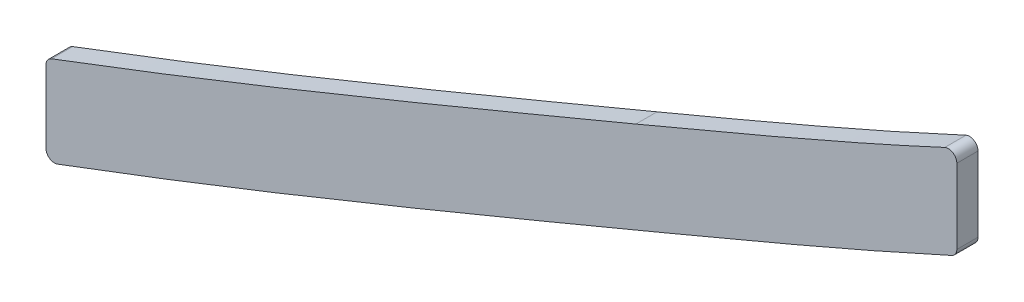
SolidWorks part; units mm, degrees
material "Balsa"
ref_plane "Front Plane" through (0, 0, 0) normal (0, 0, 1) x (1, 0, 0)
ref_plane "Top Plane" through (0, 0, 0) normal (0, 1, 0) x (1, 0, 0)
ref_plane "Right Plane" through (0, 0, 0) normal (1, 0, 0) x (0, 0, -1)
sketch "Sketch1" plane through (0, 0, 0) normal (0, 0, 1) x (1, 0, 0)
  line L0 (129.1265, 126.0779) -> (45.2335, 95.7177) construction
  line L1 (0, 0) -> (0, 656.1291) construction
  line L2 (1046.2855, -53.4707) -> (499.61, -53.4707)
  line L3 (210.5585, 160.3278) -> (162.5016, 140.2562) construction
  line L4 (103.1875, 116.7756) -> (103.1875, 13.8211)
  line L5 (239.7125, 173.3723) -> (239.7125, 18.8603)
  line L6 (239.2308, 173.1465) -> (239.7125, 173.3723)
  line L8 (244.6214, 161.6473) -> (245.1031, 161.8731) construction
  arc A3 (36.5452, 91.5722) -> (50.6762, 98.5918) centre (72.503, 36.9197) cw
  arc A4 (33.5941, 89.512) -> (36.5452, 91.5722) centre (72.5029, 36.9192) cw
  arc A5 (26.5879, 83.5209) -> (26.7433, 83.6735) centre (72.5028, 36.9189) cw
  spline S0 degree 3 poles (90.5238, 112.1079) (125.4792, 124.758) (161.5722, 139.868) (191.6078, 152.4128) knots 0 0 0 0 1 1 1 1
  spline S1 degree 1 poles (94.8455, 100.1658) (196.5024, 140.6938) knots 0 0 1 1 construction
  spline S2 degree 1 poles (196.5024, 140.6938) (244.6214, 161.6473) knots 0 0 1 1 construction
  spline S3 degree 3 poles (94.8455, 100.1658) (99.2852, 101.7725) (108.1262, 105.0368) (121.4387, 110.1165) (134.6545, 115.2971) (147.7092, 120.5264) (160.5147, 125.7437) (170.9096, 130.0328) (179.0169, 133.3991) (184.9834, 135.8842) (189.8481, 137.9146) (193.6777, 139.514) (195.5579, 140.2994) (196.5024, 140.6938) knots 0 0 0 0 0.125 0.25 0.375 0.5 0.625 0.75 0.8125 0.875 0.9375 0.96875 1 1 1 1
  spline S4 degree 3 poles (196.5024, 140.6938) (200.4723, 142.3519) (208.3835, 145.6702) (220.3642, 150.772) (230.4226, 155.1671) (238.5139, 158.8124) (242.5935, 160.6966) (244.6214, 161.6473) knots 14.81781 14.81781 14.81781 14.81781 16.034279 17.250748 18.467217 19.075451 19.683685 19.683685 19.683685 19.683685
  spline S8 degree 5 poles (191.6078, 152.4128) (201.0734, 156.3662) (210.5667, 160.3662) (220.0964, 164.4424) (229.6613, 168.6605) (239.2308, 173.1465) knots 14.81781 14.81781 14.81781 14.81781 14.81781 14.81781 19.683685 19.683685 19.683685 19.683685 19.683685 19.683685 weights 1 1 1 1 1 1
  spline S9 degree 5 poles (50.6762, 98.5918) (58.5981, 101.1149) (66.52, 103.702) (74.4715, 106.3907) (82.4705, 109.1935) (90.5238, 112.1079) knots 0 0 0 0 0 0 4.296847 4.296847 4.296847 4.296847 4.296847 4.296847 weights 1 1 1 1 1 1
  spline S10 degree 5 poles (26.7433, 83.6735) (28.0126, 84.9158) (29.3241, 86.115) (30.6979, 87.2902) (32.127, 88.4267) (33.5941, 89.512) knots 0 0 0 0 0 0 0.963167 0.963167 0.963167 0.963167 0.963167 0.963167 weights 1 1 1 1 1 1
  spline S11 degree 5 poles (18.4363, 73.7529) (19.8463, 75.8225) (21.3553, 77.8246) (22.9948, 79.8016) (24.7465, 81.7067) (26.5879, 83.5209) knots 0 0 0 0 0 0 1.402615 1.402615 1.402615 1.402615 1.402615 1.402615 weights 1 1 1 1 1 1
  spline S12 degree 5 poles (818.067, 264.7065) (827.0431, 263.4992) (836.0291, 262.3734) (845.0868, 261.3058) (891.3865, 256.087) (937.6862, 251.7792) (973.4521, 248.2277) (1071.9467, 239.0511) (1170.4413, 229.7315) (1231.7919, 224.5039) (1324.8993, 216.7906) (1418.0067, 209.0401) (1449.7429, 206.3618) (1636.9286, 190.5211) (1824.1143, 175.4092) (1979.9669, 164.2997) (2156.2686, 150.4144) (2332.5703, 133.8572) (2354.213, 131.7851) (2436.3555, 123.724) (2518.4981, 114.8591) (2579.4813, 107.7425) (2639.6368, 100.3834) (2699.7923, 92.6045) knots 77.930822 77.930822 77.930822 77.930822 77.930822 77.930822 82.465793 82.465793 82.465793 100.79329 100.79329 100.79329 131.098954 131.098954 131.098954 146.769198 146.769198 146.769198 223.533959 223.533959 223.533959 233.943117 233.943117 233.943117 264.216209 264.216209 264.216209 264.216209 264.216209 264.216209 weights 1 1 1 1 1 1 1 1 1 1 1 1 1 1 1 1 1 1 1 1 1 1 1 1
  spline S13 degree 5 poles (241.4251, -53.4707) (224.2869, -53.4707) (207.1495, -53.4673) (190.2039, -52.6866) (151.6561, -49.0319) (113.1083, -41.5037) (91.9499, -36.3426) (71.313, -30.9696) (50.6762, -24.7565) knots 0 0 0 0 0 0 8.713816 8.713816 8.713816 19.90683 19.90683 19.90683 19.90683 19.90683 19.90683 weights 1 1 1 1 1 1 1 1 1
  spline S14 degree 5 poles (499.61, -53.4707) (492.1368, -53.4707) (484.7543, -53.4707) (477.443, -53.4707) (448.5166, -53.4707) (419.5901, -53.4707) (398.3681, -53.4707) (355.6475, -53.4707) (312.927, -53.4707) (289.2351, -53.4703) (265.365, -53.4707) (241.4948, -53.4707) (241.4716, -53.4707) (241.4484, -53.4707) (241.4251, -53.4707) knots 19.90683 19.90683 19.90683 19.90683 19.90683 19.90683 23.637897 23.637897 23.637897 34.276546 34.276546 34.276546 46.401341 46.401341 46.401341 46.413154 46.413154 46.413154 46.413154 46.413154 46.413154 weights 1 1 1 1 1 1 1 1 1 1 1 1 1 1 1
  spline S15 degree 5 poles (2699.7923, -7.5245) (2639.6368, -11.6572) (2579.4813, -15.4358) (2518.4981, -19.1485) (2436.3555, -23.2524) (2354.213, -26.6315) (2332.5703, -27.481) (2156.2686, -34.3778) (1979.9669, -41.6286) (1824.1143, -52.7713) (1636.9286, -53.5796) (1449.7429, -53.454) (1418.0067, -53.4707) (1324.8993, -53.4707) (1231.7919, -53.4707) (1170.4413, -53.4707) (1108.7841, -53.4707) (1047.1269, -53.4707) (1046.8464, -53.4707) (1046.5659, -53.4707) (1046.2855, -53.4707) knots 100.654805 100.654805 100.654805 100.654805 100.654805 100.654805 130.927897 130.927897 130.927897 141.337055 141.337055 141.337055 218.101815 218.101815 218.101815 233.772059 233.772059 233.772059 264.077723 264.077723 264.077723 264.216209 264.216209 264.216209 264.216209 264.216209 264.216209 weights 1 1 1 1 1 1 1 1 1 1 1 1 1 1 1 1 1 1 1 1 1
  point P2 (0, 0)
  dimension "D1" = 72.503
  dimension "D2" = 1046.2855
  dimension "D3" = 818.067
  dimension "D4" = 103.1875
  dimension "D5" = 239.7125
  dimension "D6" = 12.7
extrude "Boss-Extrude1" add sketch "Sketch1" against normal mid plane 3.175 contours S8 S0 L4 S3 S4 L5 L6 region at (171.7204, 137.53, 0)
fillet "Fillet1" radius 1.27 4 edges at (239.7125, 159.3721, 0) (239.7125, 173.3723, 0) (103.1875, 103.2218, 0) (103.1875, 116.7756, 0)
